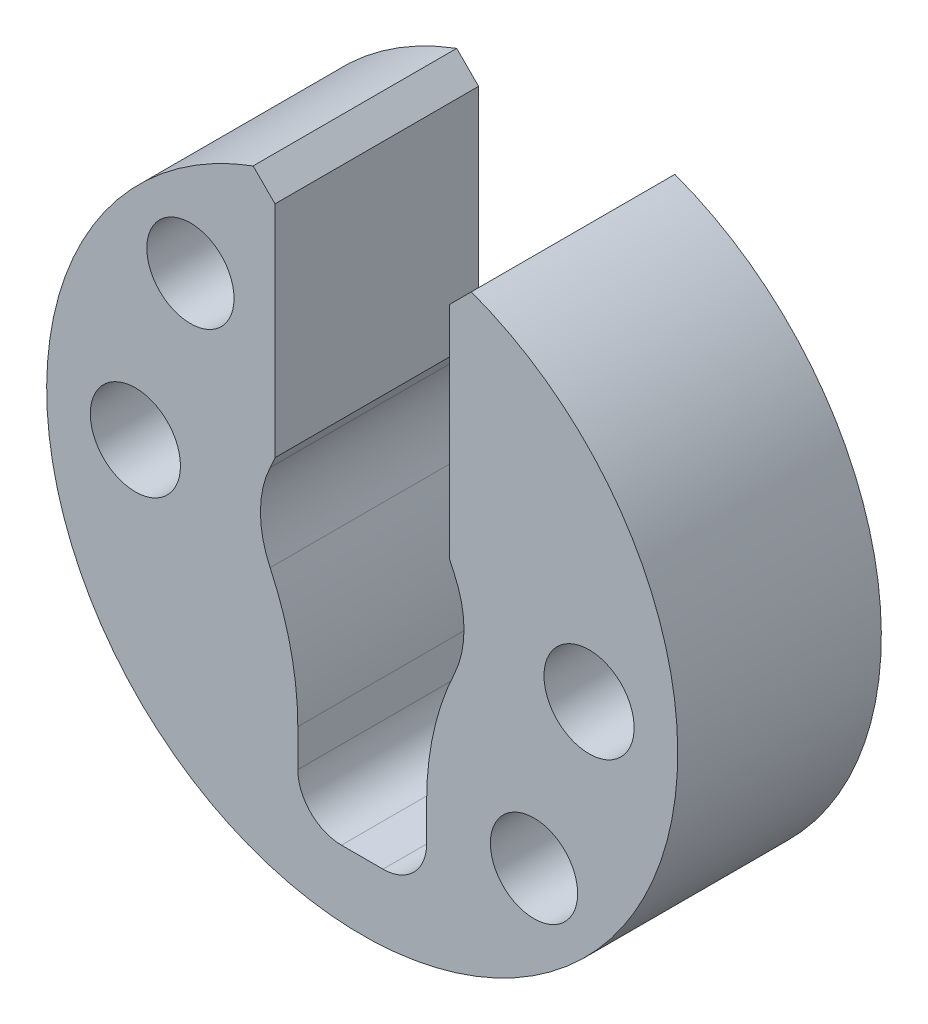
SolidWorks part; units mm, degrees
ref_plane "Front Plane" through (0, 0, 0) normal (0, 0, 1) x (1, 0, 0)
ref_plane "Top Plane" through (0, 0, 0) normal (0, 1, 0) x (1, 0, 0)
ref_plane "Right Plane" through (0, 0, 0) normal (1, 0, 0) x (0, 0, -1)
sketch "Sketch1" plane through (0, 0, 0) normal (0, 0, 1) x (1, 0, 0)
  circle A1 centre (-7.8, 0) radius 1.55
  circle A2 centre (7.8, 0) radius 1.55
  circle A3 centre (0, 0) radius 10.85
  point P0 (-7.6, 0)
  dimension "D1" = 3.1
  dimension "D2" = 0.2
extrude "Boss-Extrude1" add sketch "Sketch1" along normal blind 7
sketch "Sketch2" plane through (0, 0, 7) normal (0, 0, 1) x (1, 0, 0)
  line L0 (-2.2146, -5.7493) -> (-2.2146, -7.0272)
  line L1 (-0.7146, 9.8048) -> (0.7146, 9.8048)
  line L2 (-2.2146, 8.3048) -> (-2.2146, 5.7493)
  line L3 (-0.7146, -8.5272) -> (0.7146, -8.5272)
  line L4 (2.2146, 8.3048) -> (2.2146, 5.7493)
  line L6 (2.2146, -5.7493) -> (2.2146, -7.0272)
  arc A0 (3.1667, -1.4906) -> (3.1667, 1.4906) centre (0, 0) ccw
  arc A1 (-3.1667, 1.4906) -> (-3.1667, -1.4906) centre (0, 0) ccw
  arc A2 (-2.2146, -5.7493) -> (-3.1667, -1.4906) centre (-12.2146, -5.7493) ccw
  arc A3 (2.2146, -5.7493) -> (3.1667, -1.4906) centre (12.2146, -5.7493) cw
  arc A4 (3.1667, 1.4906) -> (2.2146, 5.7493) centre (12.2146, 5.7493) cw
  arc A5 (-2.2146, 5.7493) -> (-3.1667, 1.4906) centre (-12.2146, 5.7493) cw
  arc A6 (-0.7146, 9.8048) -> (-2.2146, 8.3048) centre (-0.7146, 8.3048) ccw
  arc A7 (0.7146, 9.8048) -> (2.2146, 8.3048) centre (0.7146, 8.3048) cw
  arc A8 (2.2146, -7.0272) -> (0.7146, -8.5272) centre (0.7146, -7.0272) cw
  arc A9 (-0.7146, -8.5272) -> (-2.2146, -7.0272) centre (-0.7146, -7.0272) cw
  point P14 (2.2146, -2.7103)
  point P19 (-2.2146, 2.7103)
  dimension "D1" = 7
  dimension "D2" = 10
  dimension "D3" = 1.5
extrude "Cut-Extrude1" cut sketch "Sketch2" against normal blind 10
sketch "Sketch3" plane through (0, 0, 0) normal (0, 0, -1) x (-1, 0, 0)
  circle A0 centre (-7.8, 0) radius 1.55
  circle A1 centre (7.8, 0) radius 1.55
extrude "Boss-Extrude2" add sketch "Sketch3" against normal blind 2.5
sketch "Sketch6" plane through (0, 0, 7) normal (0, 0, 1) x (1, 0, 0)
  line L0 (-2.998, 0) -> (2.998, 0)
  line L2 (-2.998, 0) -> (-2.998, 11.4037)
  line L3 (-2.998, 11.4037) -> (2.998, 11.4037)
  line L4 (2.998, 0) -> (2.998, 11.4037)
  point P0 (0, 0)
  dimension "D1" = 5.9959
extrude "Cut-Extrude3" cut sketch "Sketch6" against normal blind 11.5
chamfer "Chamfer2" distance 1 angle 45 2 edges at (2.998, 10.4276, 3.5) (-2.998, 10.4276, 3.5) first distance on face at (2.998, 6.1485, 3.5) first distance on face at (-2.998, 6.1485, 3.5)
sketch "Sketch7" plane through (0, 0, 7) normal (0, 0, 1) x (1, 0, 0)
  circle A1 centre (-5.9072, 5.9072) radius 1.5
  circle A2 centre (5.9072, -5.9072) radius 1.5
  point P7 (0, 0)
  dimension "D1" = 3
extrude "Cut-Extrude4" cut sketch "Sketch7" against normal blind 11.5
chamfer "Chamfer3" distance 0.5 angle 45 2 edges at (-4.4072, 5.9072, 0) (7.4072, -5.9072, 0)
